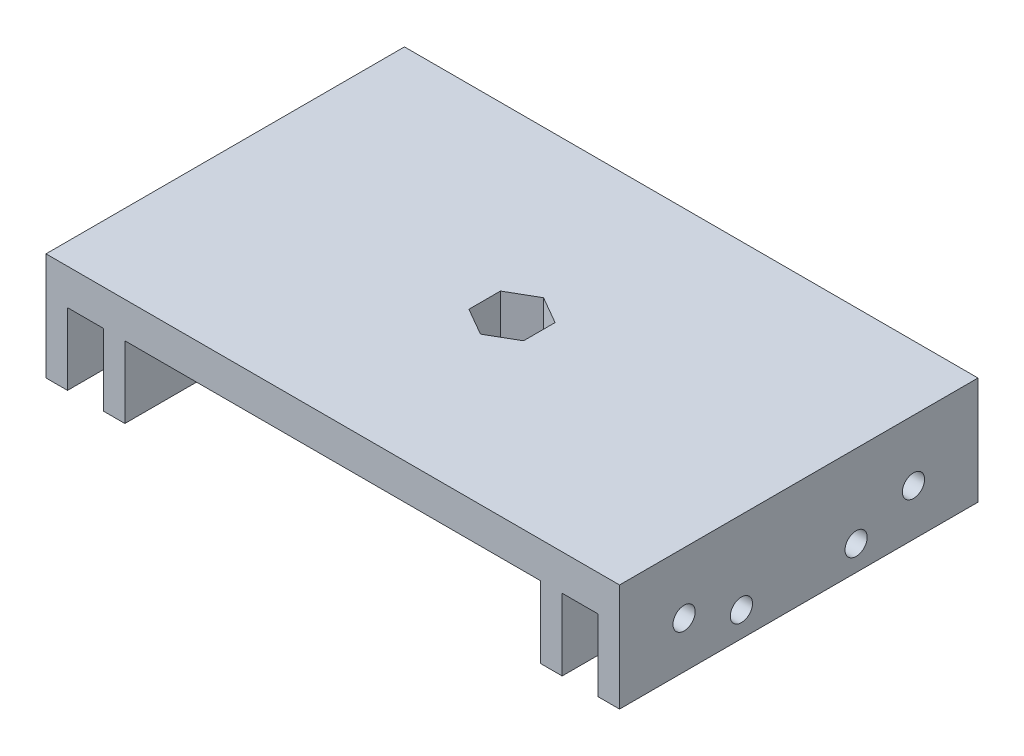
SolidWorks part; units mm, degrees
ref_plane "Front Plane" through (0, 0, 0) normal (0, 0, 1) x (1, 0, 0)
ref_plane "Top Plane" through (0, 0, 0) normal (0, 1, 0) x (1, 0, 0)
ref_plane "Right Plane" through (0, 0, 0) normal (1, 0, 0) x (0, 0, -1)
sketch "Sketch2" plane through (0, 0, 0) normal (0, 1, 0) x (1, 0, 0)
  circle A0 centre (0, 0) radius 9
extrude "Boss-Extrude1" add sketch "Sketch2" along normal blind 20
sketch "Sketch3" plane through (0, 20, 0) normal (0, 1, 0) x (1, 0, 0)
  line L0 (-3.8105, -2.2) -> (3.8105, 2.2) construction
  line L1 (0, -4.4) -> (0, 4.4) construction
  line L2 (3.8105, -2.2) -> (-3.8105, 2.2) construction
  line L15 (0, 4.4) -> (-3.8105, 2.2)
  line L16 (-3.8105, 2.2) -> (-3.8105, -2.2)
  line L17 (-3.8105, -2.2) -> (0, -4.4)
  line L18 (0, -4.4) -> (3.8105, -2.2)
  line L19 (3.8105, -2.2) -> (3.8105, 2.2)
  line L20 (3.8105, 2.2) -> (0, 4.4)
  circle A0 centre (0, 0) radius 4.4 construction
  point P4 (0, 0)
  point P5 (0, 0)
  point P6 (0, 0)
  point P9 (0, 0)
  point P10 (0, 0)
  point P11 (0, 0)
  point P14 (0, 0)
  point P15 (0, 0)
  point P17 (0, 0)
  point P20 (0, 0)
extrude "Cut-Extrude1" cut sketch "Sketch3" against normal blind 20
sketch "Sketch4" plane through (0, 20, 0) normal (0, 1, 0) x (1, 0, 0)
  line L1 (-40, 25) -> (40, 25)
  line L2 (-40, 25) -> (-40, -25)
  line L3 (-40, -25) -> (40, -25)
  line L4 (40, 25) -> (40, -25)
  line L5 (-40, 25) -> (40, -25) construction
  line L6 (-40, -25) -> (40, 25) construction
  circle A1 centre (0, 0) radius 4.5
extrude "Boss-Extrude3" add sketch "Sketch4" against normal blind 5
ref_plane "Plane3" through (0, 0, 0) normal (0.5, 0, -0.866) x (-0.866, 0, -0.5)
sketch "Sketch11" plane through (0, 0, 0) normal (0.5, 0, -0.866) x (-0.866, 0, -0.5)
  line L2 (0, 0) -> (0, 5) construction
  circle A0 centre (0, 5) radius 1.55
extrude "Cut-Extrude2" cut sketch "Sketch11" against normal blind 9 and the other way blind 9
ref_plane "Plane4" through (0, 0, 0) normal (-0.5, 0, -0.866) x (-0.866, 0, 0.5)
sketch "Sketch15" plane through (0, 0, 0) normal (-0.5, 0, -0.866) x (-0.866, 0, 0.5)
  line L0 (0, 0) -> (0, 9) construction
  circle A0 centre (0, 9) radius 1.55
extrude "Cut-Extrude9" cut sketch "Sketch15" against normal blind 9 and the other way blind 9
sketch "Sketch16" plane through (0, 15, 0) normal (0, -1, 0) x (1, 0, 0)
  line L0 (0, 0) -> (32, 0) construction
  line L6 (0, 0) -> (-32, 0) construction
  line L12 (-32, -25) -> (-32, 25)
  line L13 (-32, 25) -> (-29, 25)
  line L14 (-29, 25) -> (-29, -25)
  line L15 (-29, -25) -> (-32, -25)
  line L16 (-32, 0) -> (-37, 0) construction
  line L17 (-37, -25) -> (-37, 25)
  line L18 (-37, 25) -> (-40, 25)
  line L19 (-40, 25) -> (-40, -25)
  line L20 (-40, -25) -> (-37, -25)
  line L21 (32, -25) -> (32, 25)
  line L22 (32, 25) -> (29, 25)
  line L23 (29, 25) -> (29, -25)
  line L24 (29, -25) -> (32, -25)
  line L25 (32, 0) -> (37, 0) construction
  line L26 (37, -25) -> (37, 25)
  line L27 (37, 25) -> (40, 25)
  line L28 (40, 25) -> (40, -25)
  line L29 (40, -25) -> (37, -25)
  point P7 (-32, 0)
  point P14 (-37, 0)
  point P19 (32, 0)
  point P25 (37, 0)
extrude "Boss-Extrude4" add sketch "Sketch16" along normal blind 10
sketch "Sketch17" plane through (-40, 0, 0) normal (-1, 0, 0) x (0, 0, 1)
  line L0 (-25, 5) -> (-25, 8.5) construction
  line L1 (-25, 5) -> (-25, 20) construction
  line L2 (-25, 8.5) -> (-8, 8.5) construction
  line L3 (-8, 8.5) -> (8, 8.5) construction
  line L4 (-16, 11.5) -> (16, 11.5) construction
  line L5 (-25, 15) -> (-25, 11.5) construction
  line L6 (-25, 11.5) -> (-16, 11.5) construction
  circle A0 centre (-16, 11.5) radius 1.55
  circle A1 centre (-8, 8.5) radius 1.55
  circle A3 centre (8, 8.5) radius 1.55
  circle A5 centre (16, 11.5) radius 1.55
extrude "Cut-Extrude10" cut sketch "Sketch17" against normal up to surface (11 mm away) up to face at (-29, 10, 0)
sketch "Sketch18" plane through (40, 0, 0) normal (1, 0, 0) x (0, 0, -1)
  line L0 (-25, 5) -> (-25, 8.5) construction
  line L1 (-25, 8.5) -> (-8, 8.5) construction
  line L2 (-8, 8.5) -> (8, 8.5) construction
  line L3 (8, 8.5) -> (-8, 8.5) construction
  line L4 (-25, 15) -> (-25, 11.5) construction
  line L5 (-25, 5) -> (-25, 20) construction
  line L6 (-25, 11.5) -> (-16, 11.5) construction
  line L7 (-16, 11.5) -> (16, 11.5) construction
  line L8 (16, 11.5) -> (-16, 11.5) construction
  circle A0 centre (-8, 8.5) radius 1.55
  circle A1 centre (8, 8.5) radius 1.55
  circle A2 centre (16, 11.5) radius 1.55
  circle A3 centre (-16, 11.5) radius 1.55
extrude "Cut-Extrude11" cut sketch "Sketch18" against normal up to surface (11 mm away) up to face at (29, 10, 0)
sketch "Sketch19" plane through (0, 0, 0) normal (-0.5, 0, -0.866) x (-0.866, 0, 0.5)
  circle A0 centre (0, 9) radius 3.5
extrude "Cut-Extrude14" cut sketch "Sketch19" against normal blind 3 from offset 9 contours A0
extrude "Cut-Extrude15" cut sketch "Sketch19<3>" along normal blind 3 from offset 9 offset against normal yes
sketch "Sketch19<3>" plane through (0, 0, 0) normal (-0.5, 0, -0.866) x (-0.866, 0, 0.5) same geometry as "Sketch19"
sketch "Sketch20" plane through (0, 0, 0) normal (0.5, 0, -0.866) x (-0.866, 0, -0.5)
  circle A0 centre (0, 5) radius 3.5
extrude "Cut-Extrude16" cut sketch "Sketch20" against normal blind 3 from offset 9
extrude "Cut-Extrude17" cut sketch "Sketch20<2>" along normal blind 3 from offset 9 offset against normal yes
sketch "Sketch20<2>" plane through (0, 0, 0) normal (0.5, 0, -0.866) x (-0.866, 0, -0.5) same geometry as "Sketch20"
